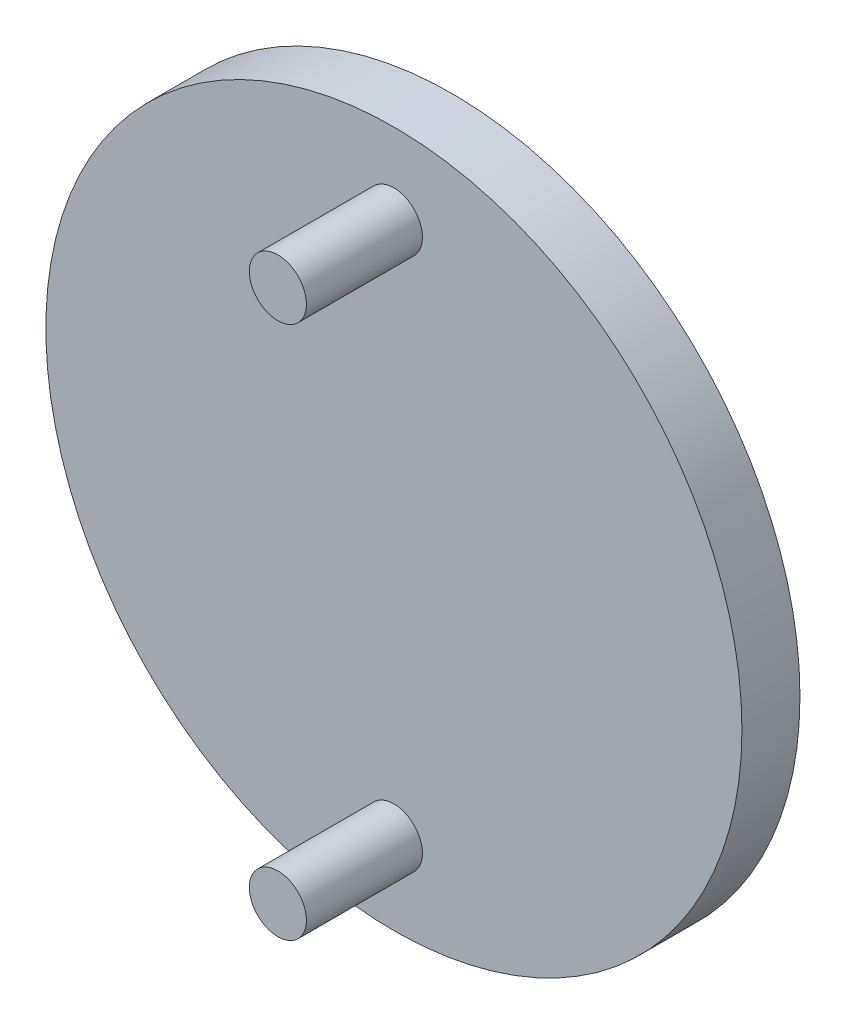
SolidWorks part; units mm, degrees
ref_plane "Front Plane" through (0, 0, 0) normal (0, 0, 1) x (1, 0, 0)
ref_plane "Top Plane" through (0, 0, 0) normal (0, 1, 0) x (1, 0, 0)
ref_plane "Right Plane" through (0, 0, 0) normal (1, 0, 0) x (0, 0, -1)
sketch "Sketch1" plane through (0, 0, 0) normal (0, 0, 1) x (1, 0, 0)
  circle A0 centre (0, 0) radius 60
  dimension "D1" = 120
extrude "Boss-Extrude1" add sketch "Sketch1" along normal blind 10
sketch "Sketch2" plane through (0, 0, 0) normal (0, 0, 1) x (1, 0, 0)
  circle A0 centre (0, 45.9849) radius 4.92
  dimension "D1" = 9.84
extrude "Boss-Extrude2" add sketch "Sketch2" along normal blind 30
ref_axis "Axis1" through (0, 0, 10) along (0, 0, -1)
pattern_circular "CirPattern1" count 2 over 360 about axis through (0, 0, 10) along (0, 0, -1) of "Boss-Extrude2"
